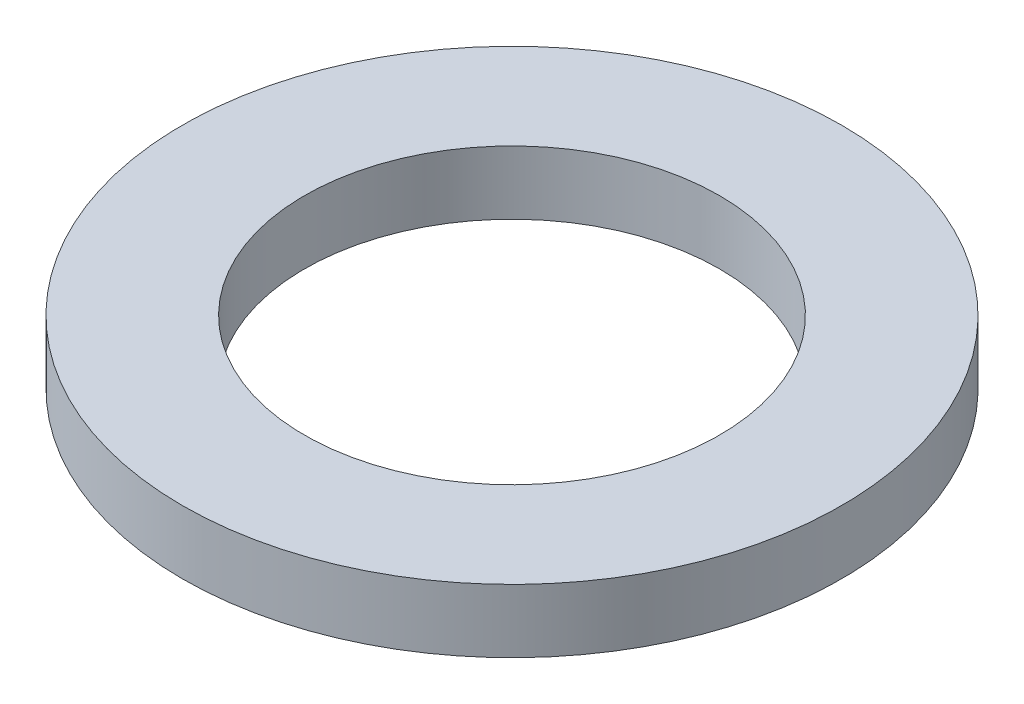
SolidWorks part; units mm, degrees
ref_plane "Front Plane" through (0, 0, 0) normal (0, 0, 1) x (1, 0, 0)
ref_plane "Top Plane" through (0, 0, 0) normal (0, 1, 0) x (1, 0, 0)
ref_plane "Right Plane" through (0, 0, 0) normal (1, 0, 0) x (0, 0, -1)
sketch "Sketch1" plane through (0, 0, 0) normal (0, 1, 0) x (1, 0, 0)
  circle A0 centre (0, 0) radius 67.5
  dimension "FLANGE_OD" = 135
extrude "Boss-Extrude1" add sketch "Sketch1" along normal blind 13
sketch "Sketch2" plane through (0, 0, 0) normal (0, 1, 0) x (1, 0, 0)
  circle A0 centre (0, 0) radius 42.5
  dimension "BORE_D" = 85
extrude "Cut-Extrude1" cut sketch "Sketch2" along normal through all
sketch "Sketch3" plane through (0, 13, 0) normal (0, 1, 0) x (1, 0, 0)
  circle A0 centre (0, 0) radius 29.1017 construction
  circle A1 centre (-29.1017, 0) radius 3.1679
  dimension "BOLT_D" = 6.3358
  dimension "BOLT_PCD" = 58.2034
extrude "Cut-Extrude2" cut sketch "Sketch3" against normal blind 10.7739 rebuild error yes
pattern_circular "CirPattern1" count 3 over 360 rebuild error yes
